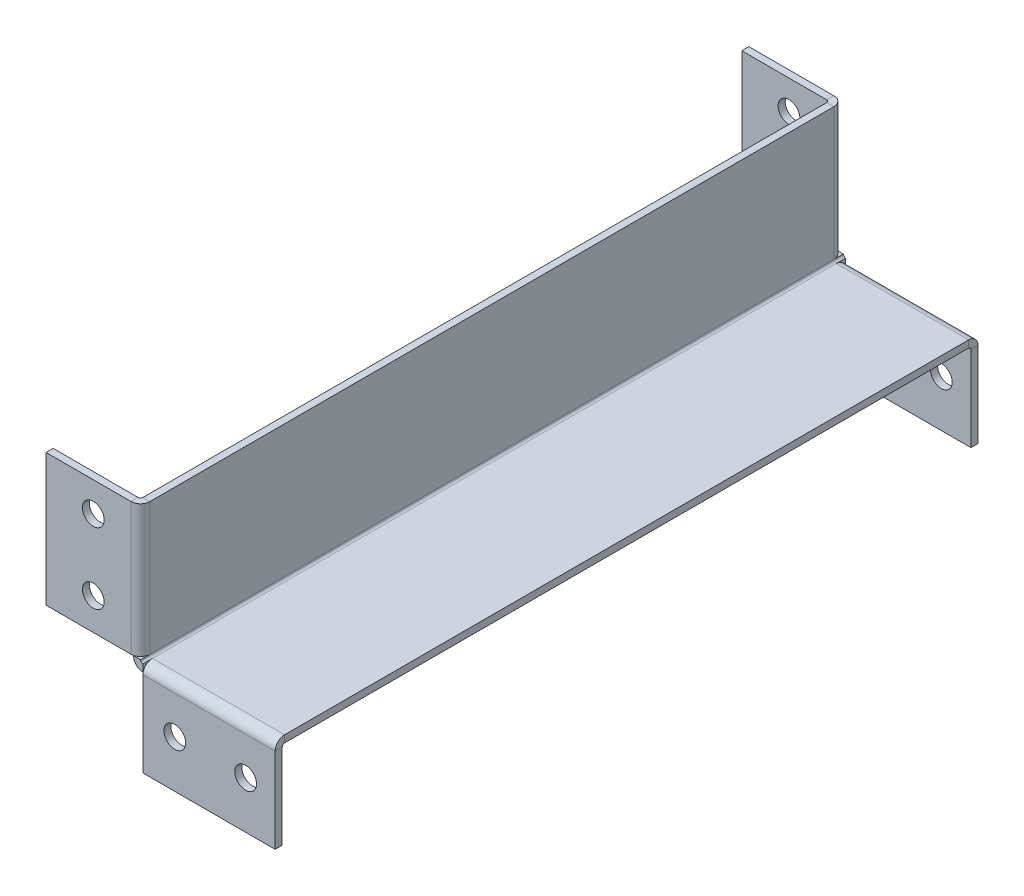
SolidWorks part; units mm, degrees
note: The reader was unsure of these and kept them because the rebuilt part matched: flange length of "Edge-Flange1", "Edge-Flange2".
ref_plane "Front Plane" through (0, 0, 0) normal (0, 0, 1) x (1, 0, 0)
ref_plane "Top Plane" through (0, 0, 0) normal (0, 1, 0) x (1, 0, 0)
ref_plane "Right Plane" through (0, 0, 0) normal (1, 0, 0) x (0, 0, -1)
sketch "Sketch1" plane through (0, 0, 0) normal (0, 1, 0) x (1, 0, 0)
  line L1 (30, 148.75) -> (-30, 148.75)
  line L2 (30, 148.75) -> (30, -148.75)
  line L3 (30, -148.75) -> (-30, -148.75)
  line L4 (-30, 148.75) -> (-30, -148.75)
  line L5 (30, 148.75) -> (-30, -148.75) construction
  line L6 (30, -148.75) -> (-30, 148.75) construction
  point P0 (0, 0)
  dimension "D1" = 60
  dimension "D2" = 297.5
sheet metal parameters "Sheet-Metal1" thickness 3 parameters "D1"=1
base flange "Base-Flange1" sketch "Sketch1" thickness 3 reverse thickness direction yes parameters "D1"=1
edge flange "Edge-Flange1" sketch "Sketch5" flange angle 90 flange length 60 flange position material inside bend radius 1 thickness 3 parameters "D6"=10
sketch "Sketch5" plane through (-30, 3, 0) normal (-1, 0, 0) x (0, 0, 1)
  line L2 (-148.75, 0) -> (-148.75, 57)
  line L3 (-148.75, 57) -> (148.75, 57)
  line L4 (148.75, 57) -> (148.75, 0)
  line L5 (-148.75, 0) -> (148.75, 0) construction
  line L6 (-148.75, 0) -> (148.75, 0)
bend "EdgeBend1" bend radius 1 bend angle 90 parameters "D5"=1
edge flange "Edge-Flange2" sketch "Sketch14" flange profiles "Sketch14", "Sketch15", "Sketch16", "Sketch17" flange angle 90 flange length 40 flange position material inside bend radius 1 thickness 3 relief none parameters "D6"=10, "D8"=0.5
sketch "Sketch14" plane through (-30, 0, 148.75) normal (0, 0, -1) x (0, -1, 0)
  line L1 (-4, 0) -> (-60, 0) construction
  line L2 (-60, 0) -> (-60, 37)
  line L3 (-60, 37) -> (-4, 37)
  line L4 (-4, 37) -> (-4, 0)
  line L5 (-4, 0) -> (-60, 0)
sketch "Sketch15" plane through (0, 0, 148.75) normal (0, 0, -1) x (1, 0, 0)
  line L0 (30, 0) -> (-26, 0) construction
  line L1 (30, 0) -> (-26, 0)
  line L2 (30, 0) -> (30, 37)
  line L3 (30, 37) -> (-26, 37)
  line L4 (-26, 37) -> (-26, 0)
sketch "Sketch16" plane through (-30, 0, -148.75) normal (0, 0, 1) x (0, 1, 0)
  line L0 (60, 0) -> (4, 0) construction
  line L1 (60, 0) -> (4, 0)
  line L2 (60, 0) -> (60, 37)
  line L3 (60, 37) -> (4, 37)
  line L4 (4, 37) -> (4, 0)
sketch "Sketch17" plane through (0, 0, -148.75) normal (0, 0, 1) x (-1, 0, 0)
  line L0 (26, 0) -> (-30, 0) construction
  line L1 (26, 0) -> (-30, 0)
  line L2 (26, 0) -> (26, 37)
  line L3 (26, 37) -> (-30, 37)
  line L4 (-30, 37) -> (-30, 0)
bend "EdgeBend2" bend radius 1 bend angle 90 parameters "D5"=2
bend "EdgeBend3" bend radius 1 bend angle 90 parameters "D5"=3
bend "EdgeBend4" bend radius 1 bend angle 90 parameters "D5"=4
bend "EdgeBend5" bend radius 1 bend angle 90 parameters "D5"=5
sketch "Sketch18" plane through (0, 0, 148.75) normal (0, 0, 1) x (1, 0, 0)
  line L0 (-26, 3) -> (30, 3) construction
  line L1 (-27, 60) -> (-27, 4) construction
  line L2 (-67, 60) -> (-31, 60) construction
  line L3 (30, -1) -> (30, -37) construction
  circle A0 centre (-47, 47.5) radius 4.6
  circle A1 centre (-47, 17.5) radius 4.6
  circle A2 centre (-12.5, -17) radius 4.6
  circle A3 centre (17.5, -17) radius 4.6
  dimension "D7" = 9.2
  dimension "D1" = 30
  dimension "D2" = 30
  dimension "D3" = 20
  dimension "D4" = 20
  dimension "D5" = 12.5
  dimension "D6" = 12.5
extrude "Extrude1" cut sketch "Sketch18" against normal through all normal cut yes
flat pattern "Flat-Pattern1" [suppressed]
sketch "Bend-Lines1" plane through (0, 4, 0) normal (0, 1, 0) x (-1, 0, 0)
  line L0 (25, -126.4012) -> (-30, -126.4012) construction
  line L1 (82.8023, -126.4012) -> (27.8023, -126.4012) construction
  line L2 (-30, 126.4012) -> (25, 126.4012) construction
  line L3 (27.8023, 126.4012) -> (82.8023, 126.4012) construction
  line L4 (26.4012, -130) -> (26.4012, 130) construction
  line L5 (25, -126.4012) -> (-30, -126.4012) construction
  line L6 (82.8023, -126.4012) -> (27.8023, -126.4012) construction
  line L7 (-30, 126.4012) -> (25, 126.4012) construction
  line L8 (27.8023, 126.4012) -> (82.8023, 126.4012) construction
  line L9 (26.4012, -130) -> (26.4012, 130) construction
bend of the flat pattern "Flatten-<EdgeBend1>1"
bend of the flat pattern "Flatten-<EdgeBend2>1"
bend of the flat pattern "Flatten-<EdgeBend3>1"
bend of the flat pattern "Flatten-<EdgeBend4>1"
bend of the flat pattern "Flatten-<EdgeBend5>1"
